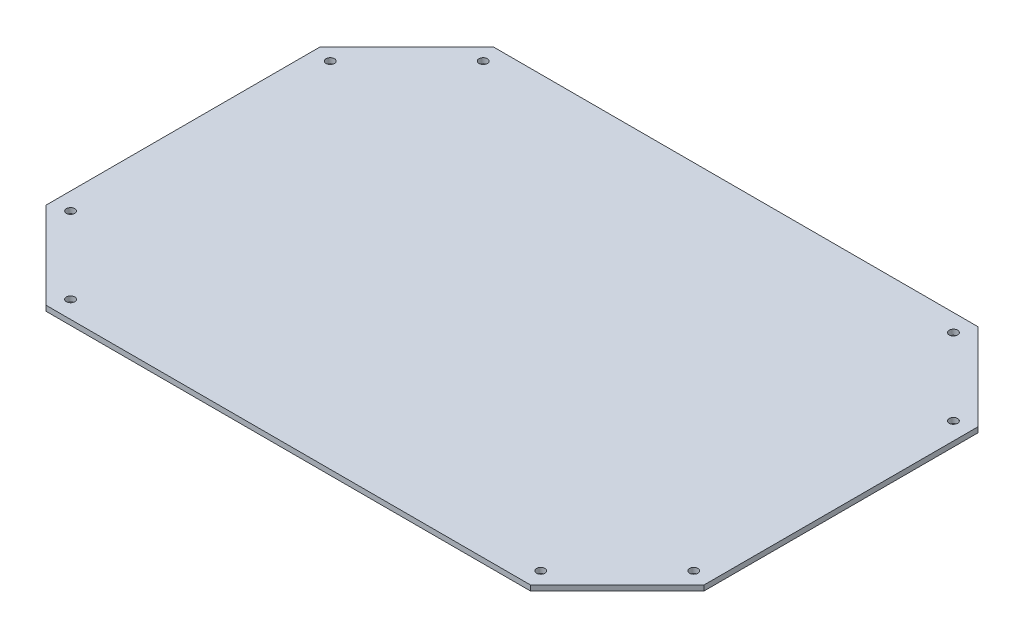
SolidWorks part; units mm, degrees
material "ABS PC"
ref_plane "Front Plane" through (0, 0, 0) normal (0, 0, 1) x (1, 0, 0)
ref_plane "Top Plane" through (0, 0, 0) normal (0, 1, 0) x (1, 0, 0)
ref_plane "Right Plane" through (0, 0, 0) normal (1, 0, 0) x (0, 0, -1)
ref_axis "X" through (-88.99, 0, 0) along (1, 0, 0)
ref_axis "Y" through (0, 55, 0) along (0, -1, 0)
ref_axis "Z" through (0, 0, -88.99) along (0, 0, 1)
sketch "Sketch1" plane through (0, 0, 0) normal (0, 1, 0) x (1, 0, 0)
  line L12 (125, 52.0711) -> (92.0711, 85)
  line L13 (92.0711, 85) -> (-92.0711, 85)
  line L14 (-92.0711, 85) -> (-125, 52.0711)
  line L15 (-125, 52.0711) -> (-125, -52.0711)
  line L16 (-125, -52.0711) -> (-92.0711, -85)
  line L17 (-92.0711, -85) -> (92.0711, -85)
  line L18 (92.0711, -85) -> (125, -52.0711)
  line L19 (125, -52.0711) -> (125, 52.0711)
  line L20 (125, 52.0711) -> (92.0711, 85)
  line L21 (92.0711, 85) -> (-92.0711, 85)
  line L22 (-92.0711, 85) -> (-125, 52.0711)
  line L23 (-125, 52.0711) -> (-125, -52.0711)
  line L24 (-125, -52.0711) -> (-92.0711, -85)
  line L25 (-92.0711, -85) -> (92.0711, -85)
  line L26 (92.0711, -85) -> (125, -52.0711)
  line L27 (125, -52.0711) -> (125, 52.0711)
  circle A0 centre (-89.3373, -78.4) radius 1.6 construction
  circle A1 centre (-118.4, -49.3373) radius 1.6 construction
  circle A2 centre (-118.4, 49.3373) radius 1.6 construction
  circle A3 centre (-89.3373, 78.4) radius 1.6 construction
  circle A4 centre (89.3373, 78.4) radius 1.6 construction
  circle A5 centre (118.4, 49.3373) radius 1.6 construction
  circle A6 centre (118.4, -49.3373) radius 1.6 construction
  circle A7 centre (89.3373, -78.4) radius 1.6 construction
  circle A8 centre (-89.3373, -78.4) radius 1.6
  circle A9 centre (-118.4, -49.3373) radius 1.6
  circle A10 centre (-118.4, 49.3373) radius 1.6
  circle A11 centre (-89.3373, 78.4) radius 1.6
  circle A12 centre (89.3373, 78.4) radius 1.6
  circle A13 centre (118.4, 49.3373) radius 1.6
  circle A14 centre (118.4, -49.3373) radius 1.6
  circle A15 centre (89.3373, -78.4) radius 1.6
  dimension "D1" = 0
extrude "Boss-Extrude1" add sketch "Sketch1" along normal blind 2
